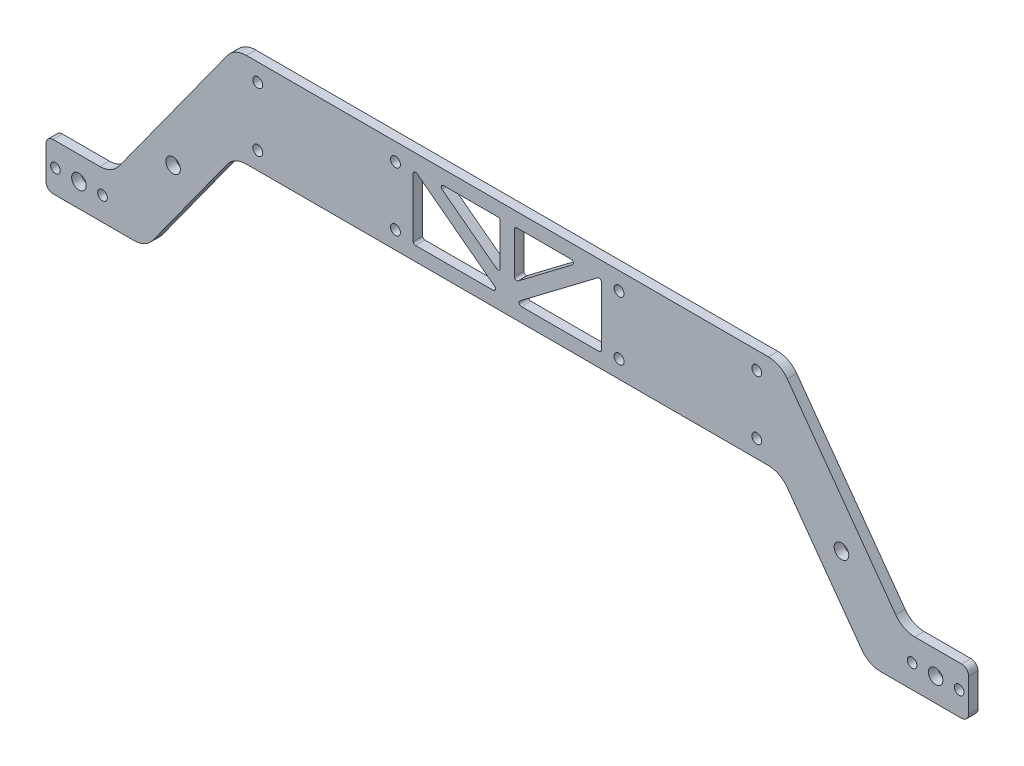
SolidWorks part; units mm, degrees
material "Thornel Mat VMA"
ref_plane "前视基准面" through (0, 0, 0) normal (0, 0, 1) x (1, 0, 0)
ref_plane "上视基准面" through (0, 0, 0) normal (0, 1, 0) x (1, 0, 0)
ref_plane "右视基准面" through (0, 0, 0) normal (1, 0, 0) x (0, 0, -1)
other "Configuration Table"
sketch "草图1" plane through (0, 0, 0) normal (0, 0, 1) x (1, 0, 0)
  line L1 (-47.5, -12.5) -> (47.5, -12.5) construction
  line L2 (-47.5, -12.5) -> (-47.5, 12.5) construction
  line L3 (-47.5, 12.5) -> (47.5, 12.5) construction
  line L4 (47.5, -12.5) -> (47.5, 12.5) construction
  line L5 (-47.5, -12.5) -> (47.5, 12.5) construction
  line L6 (-47.5, 12.5) -> (47.5, -12.5) construction
  line L7 (-116, -20) -> (116, -20)
  line L8 (-116, -20) -> (-116, 20)
  line L9 (-116, 20) -> (116, 20)
  line L10 (116, -20) -> (116, 20)
  line L11 (-116, -20) -> (116, 20) construction
  line L12 (-116, 20) -> (116, -20) construction
  circle A0 centre (-47.5, 12.5) radius 2.1
  circle A1 centre (47.5, 12.5) radius 2.1
  circle A2 centre (-47.5, -12.5) radius 2.1
  circle A3 centre (47.5, -12.5) radius 2.1
  point P0 (0, 0)
  point P10 (0, 0)
  dimension "D1" = 4.2
  dimension "D2" = 95
  dimension "D3" = 25
  dimension "D4" = 40
  dimension "D5" = 232
extrude "凸台-拉伸1" add sketch "草图1" along normal blind 4
sketch "草图2" plane through (0, 0, 4) normal (0, 0, 1) x (1, 0, 0)
  line L0 (-116, 20) -> (-168, -52)
  line L1 (-168, -52) -> (-196, -52)
  line L2 (-196, -52) -> (-196, -72)
  line L3 (-196, -72) -> (-153.5556, -72)
  line L4 (-153.5556, -72) -> (-116, -20)
  line L5 (-116, 20) -> (-116, -20)
  line L6 (0, -1000) -> (0, 49000) construction
  line L7 (116, 20) -> (168, -52)
  line L8 (168, -52) -> (196, -52)
  line L9 (196, -52) -> (196, -72)
  line L10 (196, -72) -> (153.5556, -72)
  line L11 (153.5556, -72) -> (116, -20)
  line L12 (116, 20) -> (116, -20)
  line L13 (-116, 0) -> (-168, -72) construction
  circle A0 centre (-142, -36) radius 3.1
  circle A1 centre (142, -36) radius 3.1
  dimension "D5" = 6.2
  dimension "D1" = 52
  dimension "D2" = 72
  dimension "D3" = 20
  dimension "D4" = 28
extrude "凸台-拉伸2" add sketch "草图2" against normal up to surface (4 mm away) up to face at (-45.4, -12.5, 0)
sketch "草图4" plane through (0, 0, 4) normal (0, 0, 1) x (1, 0, 0)
  line L0 (0, 0) -> (50000, 0) construction
  line L1 (-116, -20) -> (116, -20) construction
  line L2 (-116, 20) -> (-96, 20) construction
  line L3 (-116, 20) -> (-116, -20) construction
  line L4 (-116, -20) -> (-96, -20) construction
  line L5 (-96, 20) -> (-96, -20) construction
  line L6 (-116, 20) -> (-96, -20) construction
  line L7 (116, 20) -> (96, 20) construction
  line L8 (116, 20) -> (116, -20) construction
  line L9 (116, -20) -> (96, -20) construction
  line L10 (96, 20) -> (96, -20) construction
  line L11 (96, -20) -> (116, 20) construction
  line L12 (-106, 20) -> (-106, -20) construction
  line L13 (106, 20) -> (106, -20) construction
  line L14 (-106, 12.5) -> (-47.5, 12.5) construction
  line L15 (-106, 12.5) -> (106, 12.5) construction
  line L16 (-106, 12.5) -> (-106, -12.5) construction
  line L17 (-106, -12.5) -> (106, -12.5) construction
  line L18 (106, 12.5) -> (106, -12.5) construction
  line L19 (-106, -12.5) -> (-47.5, -12.5) construction
  circle A1 centre (-106, 12.5) radius 2.1
  circle A2 centre (-106, -12.5) radius 2.1
  circle A3 centre (106, 12.5) radius 2.1
  circle A4 centre (106, -12.5) radius 2.1
  dimension "D2" = 4.2
  dimension "D1" = 20
extrude "切除-拉伸2" cut sketch "草图4" against normal blind 10
fillet "圆角1" radius 3 4 edges at (196, -72, 2) (196, -52, 2) (-196, -52, 2) (-196, -72, 2)
fillet "圆角2" radius 10 8 edges at (168, -52, 2) (116, 20, 2) (-116, 20, 2) (-168, -52, 2) (-153.5556, -72, 2) (-116, -20, 2) (116, -20, 2) (153.5556, -72, 2)
sketch "草图5" plane through (0, 0, 4) normal (0, 0, 1) x (1, 0, 0)
  line L0 (0, 0) -> (0, -50000) construction
  line L1 (-106, 12.5) -> (-106, -12.5) construction
  line L2 (110.8869, 20) -> (-110.8869, 20) construction
  line L7 (-110.8869, -20) -> (110.8869, -20) construction
  line L8 (-40, 14) -> (-40, -14)
  line L9 (-40, -14) -> (-3, -14)
  line L10 (-3, -14) -> (-40, 14)
  line L11 (-30.0571, 14) -> (-3, -6.4756)
  line L12 (-3, -6.4756) -> (-3, 14)
  line L13 (-3, 14) -> (-30.0571, 14)
  line L14 (-40, 14) -> (-30.0571, 14) construction
  line L15 (-3, -6.4756) -> (-3, -14) construction
  line L20 (40, -14) -> (3, -14)
  line L21 (40, 14) -> (40, -14)
  line L22 (3, -14) -> (40, 14)
  line L23 (3, -6.4756) -> (3, 14)
  line L24 (30.0571, 14) -> (3, -6.4756)
  line L25 (3, 14) -> (30.0571, 14)
  line L26 (-3, 14) -> (3, 14)
  line L27 (-3, -6.4756) -> (0, -8.7459)
  line L28 (0, -8.7459) -> (3, -6.4756)
  circle A0 centre (-47.5, 12.5) radius 2.1 construction
  dimension "D7" = 7.5
  dimension "D1" = 6
  dimension "D2" = 6
  dimension "D5" = 3
  dimension "D6" = 6
sketch "草图6" plane through (0, 0, 4) normal (0, 0, 1) x (1, 0, 0)
  line L0 (-196, -62) -> (-192, -62) construction
  line L1 (-196, -55) -> (-196, -69) construction
  line L2 (-192, -62) -> (-172, -62) construction
  line L6 (0, 0) -> (0, -50000) construction
  line L10 (192, -62) -> (172, -62) construction
  line L11 (196, -62) -> (192, -62) construction
  circle A0 centre (-192, -62) radius 2.05
  circle A1 centre (-172, -62) radius 2.05
  circle A6 centre (172, -62) radius 2.05
  circle A7 centre (192, -62) radius 2.05
  circle A8 centre (-182, -62) radius 3.1
  circle A9 centre (182, -62) radius 3.1
  dimension "D3" = 4.1
  dimension "D4" = 6.2
  dimension "D1" = 4
  dimension "D2" = 20
extrude "切除-拉伸4" cut sketch "草图6" against normal through all
extrude "切除-拉伸5" cut sketch "草图5" against normal blind 10 contours L9 L10 L8 | L12 L13 L11 | L25 L23 L24 | L22 L20 L21 region at (-27.6667, -4.6667, 4) region at (-12.019, 7.1748, 4) region at (12.019, 7.1748, 4) region at (27.6667, -4.6667, 4)
fillet "圆角3" radius 1 12 edges at (3, -6.4756, 2) (3, 14, 2) (30.0571, 14, 2) (40, -14, 2) (3, -14, 2) (40, 14, 2) (-40, -14, 2) (-40, 14, 2) (-3, -14, 2) (-30.0571, 14, 2) (-3, 14, 2) (-3, -6.4756, 2)
